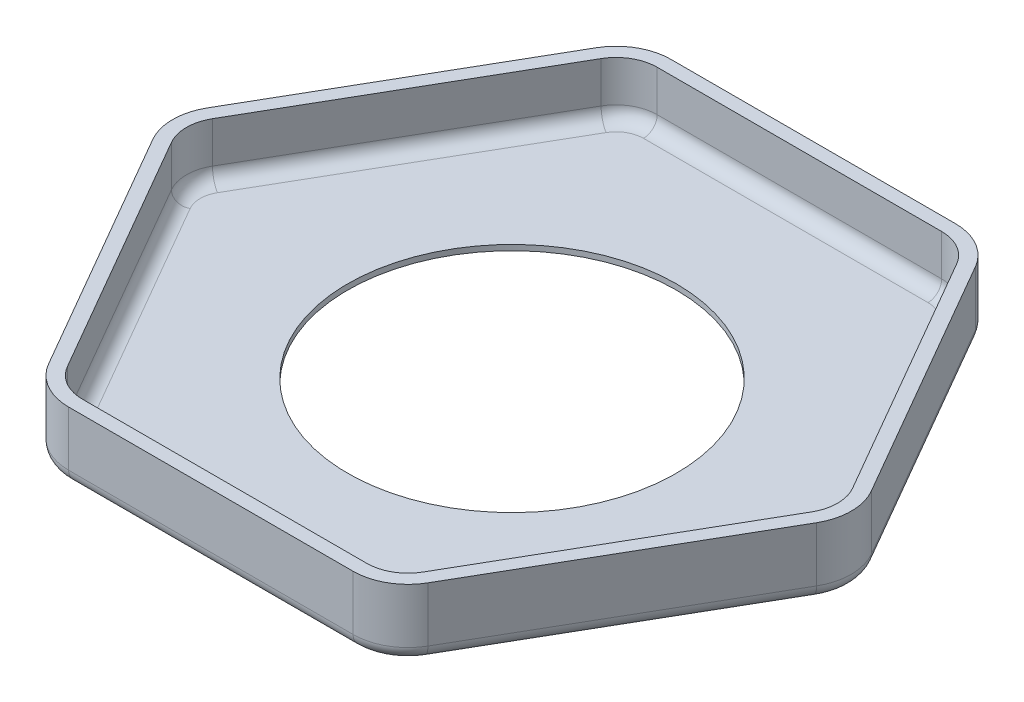
SolidWorks part; units mm, degrees
ref_plane "Front" through (0, 0, 0) normal (0, 0, 1) x (1, 0, 0)
ref_plane "Top" through (0, 0, 0) normal (0, 1, 0) x (1, 0, 0)
ref_plane "Right" through (0, 0, 0) normal (1, 0, 0) x (0, 0, -1)
sketch "Croquis1" plane through (0, 0, 0) normal (0, 1, 0) x (1, 0, 0)
  line L0 (-119.2242, -9.3942) -> (-67.2627, -99.3942)
  line L1 (-49.9422, -109.3942) -> (53.9809, -109.3942)
  line L2 (71.3014, -99.3942) -> (123.2629, -9.3942)
  line L3 (123.2629, 10.6058) -> (71.3014, 100.6058)
  line L4 (53.9809, 110.6058) -> (-49.9422, 110.6058)
  line L5 (-67.2627, 100.6058) -> (-119.2242, 10.6058)
  circle A0 centre (2.0194, 0.6058) radius 110 construction
  arc A1 (-67.2627, 100.6058) -> (-49.9422, 110.6058) centre (-49.9422, 90.6058) cw
  arc A2 (71.3014, 100.6058) -> (53.9809, 110.6058) centre (53.9809, 90.6058) ccw
  arc A3 (123.2629, -9.3942) -> (123.2629, 10.6058) centre (105.9424, 0.6058) ccw
  arc A4 (53.9809, -109.3942) -> (71.3014, -99.3942) centre (53.9809, -89.3942) ccw
  arc A5 (-67.2627, -99.3942) -> (-49.9422, -109.3942) centre (-49.9422, -89.3942) ccw
  arc A6 (-119.2242, -9.3942) -> (-119.2242, 10.6058) centre (-101.9037, 0.6058) cw
  dimension "D1" = 220
  dimension "D2" = 20
extrude "Saliente-Extruir2" add sketch "Croquis1" along normal blind 5
sketch "Croquis2" plane through (0, 5, 0) normal (0, 1, 0) x (1, 0, 0)
  line L6 (-62.9325, 98.1058) -> (-114.8941, 8.1058)
  line L7 (-114.8941, -6.8942) -> (-62.9325, -96.8942)
  line L8 (-49.9422, -104.3942) -> (53.9809, -104.3942)
  line L9 (66.9713, -96.8942) -> (118.9328, -6.8942)
  line L10 (118.9328, 8.1058) -> (66.9713, 98.1058)
  line L11 (53.9809, 105.6058) -> (-49.9422, 105.6058)
  line L12 (-67.2627, 100.6058) -> (-119.2242, 10.6058)
  line L13 (-119.2242, -9.3942) -> (-67.2627, -99.3942)
  line L14 (-49.9422, -109.3942) -> (53.9809, -109.3942)
  line L15 (71.3014, -99.3942) -> (123.2629, -9.3942)
  line L16 (123.2629, 10.6058) -> (71.3014, 100.6058)
  line L17 (53.9809, 110.6058) -> (-49.9422, 110.6058)
  line L18 (-67.2627, 100.6058) -> (-119.2242, 10.6058)
  line L19 (-119.2242, -9.3942) -> (-67.2627, -99.3942)
  line L20 (-49.9422, -109.3942) -> (53.9809, -109.3942)
  line L21 (71.3014, -99.3942) -> (123.2629, -9.3942)
  line L22 (123.2629, 10.6058) -> (71.3014, 100.6058)
  line L23 (53.9809, 110.6058) -> (-49.9422, 110.6058)
  arc A6 (-114.8941, 8.1058) -> (-114.8941, -6.8942) centre (-101.9037, 0.6058) ccw
  arc A7 (-62.9325, -96.8942) -> (-49.9422, -104.3942) centre (-49.9422, -89.3942) ccw
  arc A8 (53.9809, -104.3942) -> (66.9713, -96.8942) centre (53.9809, -89.3942) ccw
  arc A9 (118.9328, -6.8942) -> (118.9328, 8.1058) centre (105.9424, 0.6058) ccw
  arc A10 (66.9713, 98.1058) -> (53.9809, 105.6058) centre (53.9809, 90.6058) ccw
  arc A11 (-49.9422, 105.6058) -> (-62.9325, 98.1058) centre (-49.9422, 90.6058) ccw
  arc A12 (-49.9422, 110.6058) -> (-67.2627, 100.6058) centre (-49.9422, 90.6058) ccw
  arc A13 (-119.2242, 10.6058) -> (-119.2242, -9.3942) centre (-101.9037, 0.6058) ccw
  arc A14 (-67.2627, -99.3942) -> (-49.9422, -109.3942) centre (-49.9422, -89.3942) ccw
  arc A15 (53.9809, -109.3942) -> (71.3014, -99.3942) centre (53.9809, -89.3942) ccw
  arc A16 (123.2629, -9.3942) -> (123.2629, 10.6058) centre (105.9424, 0.6058) ccw
  arc A17 (71.3014, 100.6058) -> (53.9809, 110.6058) centre (53.9809, 90.6058) ccw
  arc A18 (-49.9422, 110.6058) -> (-67.2627, 100.6058) centre (-49.9422, 90.6058) ccw
  arc A19 (-119.2242, 10.6058) -> (-119.2242, -9.3942) centre (-101.9037, 0.6058) ccw
  arc A20 (-67.2627, -99.3942) -> (-49.9422, -109.3942) centre (-49.9422, -89.3942) ccw
  arc A21 (53.9809, -109.3942) -> (71.3014, -99.3942) centre (53.9809, -89.3942) ccw
  arc A22 (123.2629, -9.3942) -> (123.2629, 10.6058) centre (105.9424, 0.6058) ccw
  arc A23 (71.3014, 100.6058) -> (53.9809, 110.6058) centre (53.9809, 90.6058) ccw
  dimension "D1" = 0
  dimension "D2" = 5
extrude "Saliente-Extruir3" add sketch "Croquis2" along normal blind 20
fillet "Redondeo2" radius 5 12 edges at (-93.2434, 0, -55.6058) (-121.9037, 0, -0.6058) (-93.2434, 0, 54.3942) (-59.9422, 0, 106.7147) (2.0194, 0, 109.3942) (63.9809, 0, 106.7147) (97.2822, 0, 54.3942) (125.9424, 0, -0.6058) (97.2822, 0, -55.6058) (63.9809, 0, -107.9263) (2.0194, 0, -110.6058) (-59.9422, 0, -107.9263)
fillet "Redondeo3" radius 5 12 edges at (61.4809, 5, -103.5962) (92.952, 5, -53.1058) (120.9424, 5, -0.6058) (92.952, 5, 51.8942) (61.4809, 5, 102.3846) (2.0194, 5, 104.3942) (-57.4422, 5, 102.3846) (-88.9133, 5, 51.8942) (-116.9037, 5, -0.6058) (-88.9133, 5, -53.1058) (-57.4422, 5, -103.5962) (2.0194, 5, -105.6058)
sketch "Croquis3" plane through (0, 0, 0) normal (0, -1, 0) x (1, 0, 0)
  line L0 (-57.4422, 102.3846) -> (61.4809, -103.5962) construction
  line L1 (-57.4422, -103.5962) -> (61.4809, 102.3846) construction
  arc A0 (-49.9422, 104.3942) -> (-62.9325, 96.8942) centre (-49.9422, 89.3942) ccw construction
  arc A1 (53.9809, -105.6058) -> (66.9713, -98.1058) centre (53.9809, -90.6058) ccw construction
  arc A2 (-62.9325, -98.1058) -> (-49.9422, -105.6058) centre (-49.9422, -90.6058) ccw construction
  arc A3 (66.9713, 96.8942) -> (53.9809, 104.3942) centre (53.9809, 89.3942) ccw construction
  circle A4 centre (2.0194, -0.6058) radius 90
sketch "Croquis4" plane through (0, 0, 0) normal (0, -1, 0) x (-1, 0, 0)
  circle A0 centre (-2.0194, 0.6058) radius 60
extrude "Cortar-Extruir1" cut sketch "Croquis4" against normal blind 10
extrude "Cortar-Extruir2" cut sketch "Croquis3" against normal blind 3
